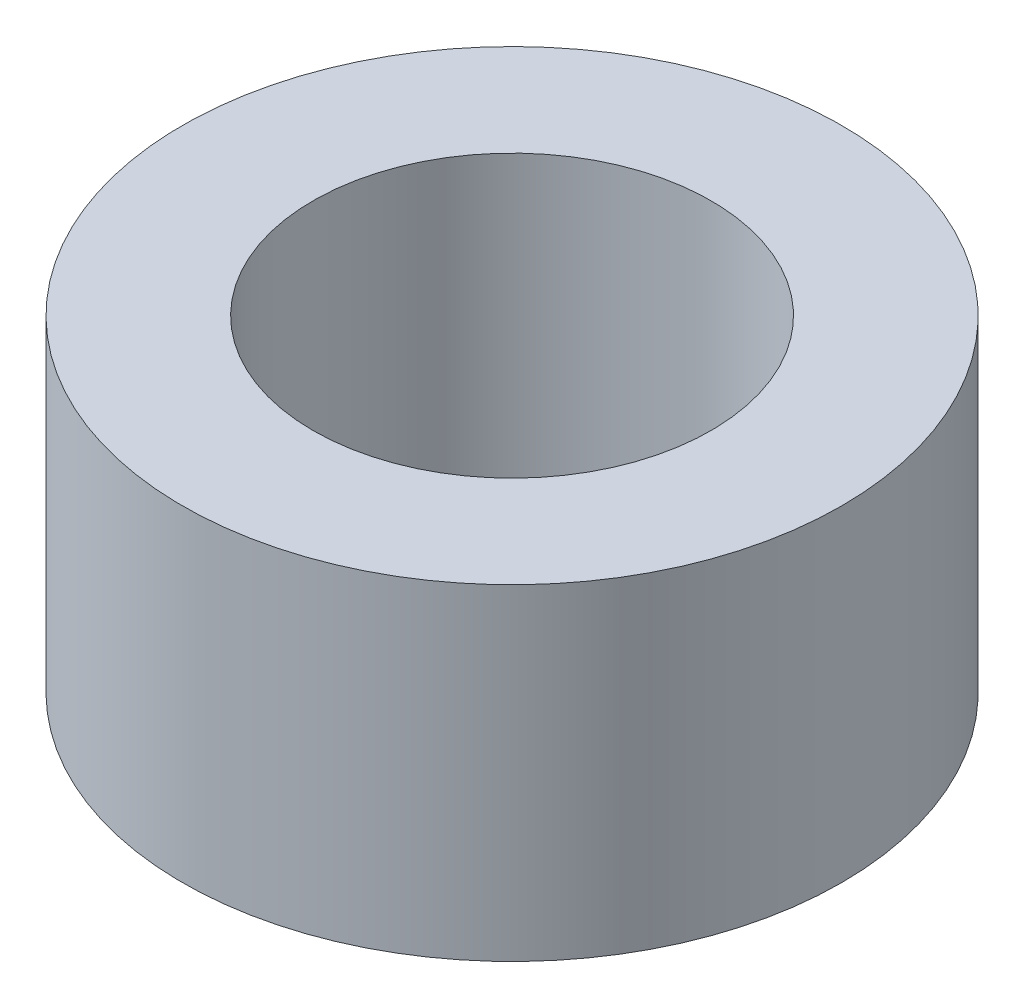
SolidWorks part; units mm, degrees
material "ABS"
ref_plane "Front Plane" through (0, 0, 0) normal (0, 0, 1) x (1, 0, 0)
ref_plane "Top Plane" through (0, 0, 0) normal (0, 1, 0) x (1, 0, 0)
ref_plane "Right Plane" through (0, 0, 0) normal (1, 0, 0) x (0, 0, -1)
sketch "Sketch1" plane through (0, 0, 0) normal (0, 1, 0) x (1, 0, 0)
  circle A0 centre (0, 0) radius 3.05
  dimension "D1" = 6.1
extrude "Extrude-Thin1" add sketch "Sketch1" along normal blind 5 thin thin type one direction wall 2
